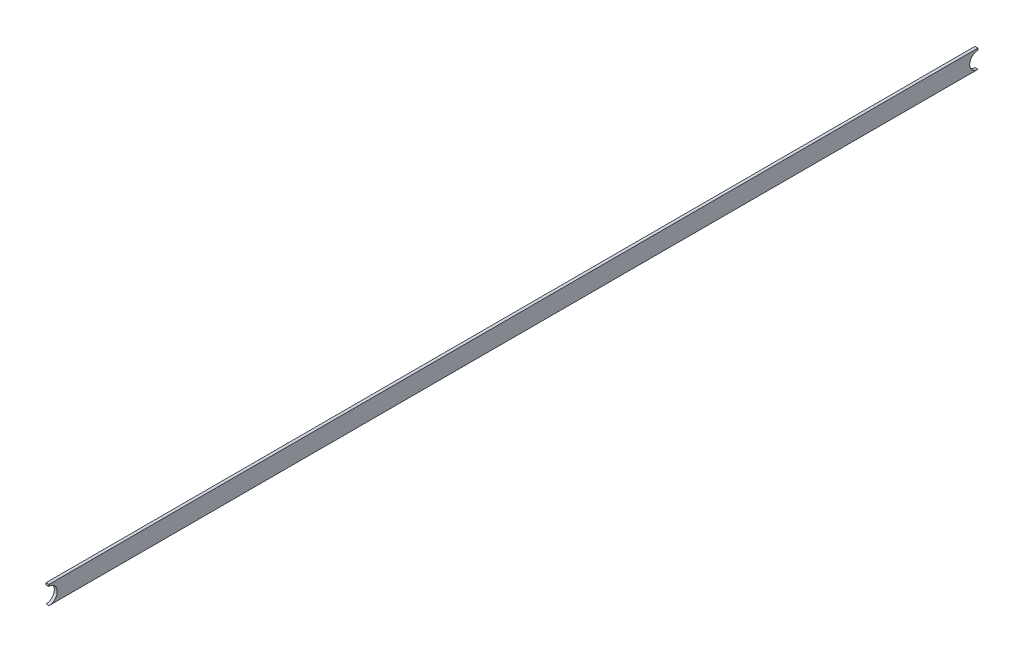
SolidWorks part; units mm, degrees
material "12Х18Н10Т ГОСТ 4543-71"
ref_plane "Спереди" through (0, 0, 0) normal (0, 0, 1) x (1, 0, 0)
ref_plane "Сверху" through (0, 0, 0) normal (0, 1, 0) x (1, 0, 0)
ref_plane "Справа" through (0, 0, 0) normal (1, 0, 0) x (0, 0, -1)
sketch "Эскиз1" plane through (0, 0, 0) normal (0, 0, 1) x (1, 0, 0)
  line L1 (-4, 25) -> (4, 25)
  line L2 (-4, 25) -> (-4, -25)
  line L3 (-4, -25) -> (4, -25)
  line L4 (4, 25) -> (4, -25)
  line L5 (0, -25) -> (0, 25) construction
  line L6 (-4, 0) -> (4, 0) construction
  point P64 (0, 0)
  dimension "D1" = 8
  dimension "D2" = 50
extrude "Бобышка-Вытянуть1" add sketch "Эскиз1" along normal mid plane 2475
sketch "Эскиз2" plane through (4, 0, 0) normal (1, 0, 0) x (0, 0, -1)
  line L0 (-1237.5, -25) -> (1237.5, -25) construction
  line L1 (-1237.5, -25) -> (-1237.5, 25) construction
  line L2 (-1237.5, 25) -> (-1260, 25)
  line L3 (-1237.5, -25) -> (-1260, -25)
  line L4 (-1260, 25) -> (-1260, 20)
  line L5 (-1237.5, -25) -> (-1237.5, 25)
  arc A0 (-1260, -25) -> (-1260, 20) centre (-1260, -2.5) ccw
  line M3 (-1237.5, 25) -> (-1237.5, -25)
  dimension "D1" = 45
extrude "Бобышка-Вытянуть2" add sketch "Эскиз2" against normal up to surface (8 mm away) contours A0 L2 L4 M3 | A0 L3 L5 region at (4, 18.8028, 1245.6922) region at (4, -19.9742, 1242.5258) up to face at (-4, 0, 0)
mirror "Зеркальное отражение1" about plane through (0, 0, 0) normal (0, 0, 1) of "Бобышка-Вытянуть2"
equation "\"расстояние между опорами фермы\"= 49"
equation "\"центр боковых направляющих\"= 1210 / 2"
equation "\"толщина полосы\"= 8"
equation "\"ширина полосы\"= 50"
equation "\"ширина боковой направляющей\"= 100 / 2"
equation "\"расстояние между центрами фиксатора\"= 178 / 2"
equation "\"D1@Эскиз1\"=\"толщина полосы\""
equation "\"D2@Эскиз1\"=\"ширина полосы\""
